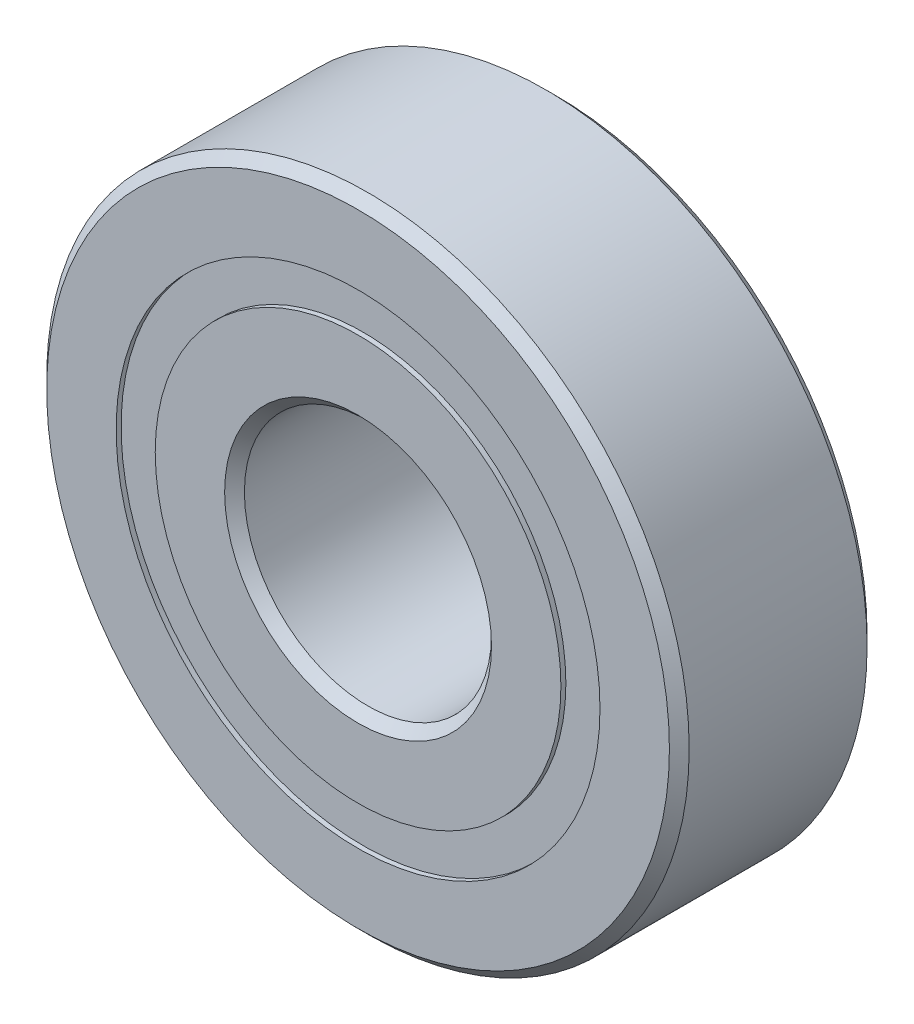
SolidWorks part; units mm, degrees
ref_plane "Front Plane" through (0, 0, 0) normal (0, 0, 1) x (1, 0, 0)
ref_plane "Top Plane" through (0, 0, 0) normal (0, 1, 0) x (1, 0, 0)
ref_plane "Right Plane" through (0, 0, 0) normal (1, 0, 0) x (0, 0, -1)
sketch "Sketch1" plane through (0, 0, 0) normal (1, 0, 0) x (0, 0, -1)
  line L0 (-4, 0) -> (4, 0) construction
  line L1 (0, 13) -> (0, -13) construction
  line L2 (3.6, 13) -> (-3.6, 13)
  line L3 (-3.6, 13) -> (-4, 12.6)
  line L5 (1.7778, 12.6) -> (4, 12.6)
  line L8 (3.6, 13) -> (4, 12.6)
  line L9 (0, 13) -> (0, 9) construction
  line L10 (0, 9) -> (0, 5) construction
  line L11 (-4, 12.6) -> (-1.7778, 12.6)
  line L13 (-1.7778, 9.7912) -> (-1.7778, 12.6)
  line L14 (1.7778, 9.7912) -> (1.7778, 12.6)
  arc A0 (-1.7778, 9.7912) -> (1.7778, 9.7912) centre (0, 9) cw
  point P14 (0, 5)
  dimension "D3" = 3.5556
  dimension "Width" = 8
  dimension "OD" = 26
  dimension "D2" = 0.4
  dimension "Shaft Dia" = 10
revolve "Revolve1" add sketch "Sketch1" angle 360 about L0
sketch "Sketch3" plane through (0, 0, 0) normal (1, 0, 0) x (0, 0, -1)
  line L3 (-4, 5.4) -> (-4, 8.2088)
  line L4 (-3.6, 13) -> (-4, 12.6) construction
  line L5 (-4, 5.4) -> (-3.6, 5)
  line L6 (-3.6, 5) -> (3.6, 5)
  line L7 (3.6, 13) -> (3.6, -13) construction
  line L8 (3.6, 5) -> (4, 5.4)
  line L10 (4, 5.4) -> (4, 8.2088)
  line L12 (0, 0) -> (0, 5) construction
  line L13 (3.6, 13) -> (4, 12.6) construction
  line L16 (-4, 8.2088) -> (-1.7778, 8.2088)
  line L18 (1.7778, 8.2088) -> (4, 8.2088)
  arc A2 (-1.7778, 8.2088) -> (1.7778, 8.2088) centre (0, 9) ccw
  dimension "D1" = 3.2088
revolve "Revolve3" add sketch "Sketch3" angle 360 about L0
sketch "Sketch4" plane through (0, 0, 0) normal (1, 0, 0) x (0, 0, -1)
  line L0 (-1.9459, 9) -> (1.9459, 9)
  arc A2 (-1.9459, 9) -> (1.9459, 9) centre (0, 9) cw
  arc A3 (1.7778, 9.7912) -> (-1.7778, 9.7912) centre (0, 9) ccw construction
revolve "Revolve4" add sketch "Sketch4" angle 360 about L0
ref_axis "Axis1" through (0, 0, -4) along (0, 0, 1)
pattern_circular "CirPattern1" count 12 over 360 about axis through (0, 0, -4) along (0, 0, 1) of bodies 104
sketch "Sketch6" plane through (0, 0, 0) normal (1, 0, 0) x (0, 0, -1)
  line L1 (-3.8, 9.79) -> (-4, 9.79)
  line L2 (-4, 12.6) -> (-4, -12.6) construction
  line L3 (-4, 9.79) -> (-4, 12.6)
  line L4 (3.8, 9.79) -> (4, 9.79)
  line L7 (4, 12.6) -> (4, -12.6) construction
  line L8 (-4, 8.2088) -> (4, 8.2088) construction
  line L9 (4, 9.79) -> (4, 12.6)
  line L12 (-3.6, 13) -> (-4, 12.6) construction
  line L13 (-4, 12.6) -> (4, 12.6)
  line L15 (-3.8, 8.21) -> (-3.8, 9.79)
  line L16 (1.9459, 9.1265) -> (1.9459, 8.21)
  line L17 (-1.9459, 9.1265) -> (-1.9459, 8.21)
  line L18 (3.8, 8.21) -> (3.8, 9.79)
  line L21 (-3.8, 8.21) -> (-1.9459, 8.21)
  line L22 (3.8, 8.21) -> (1.9459, 8.21)
  arc A0 (1.9459, 9.1265) -> (-1.9459, 9.1265) centre (0, 9) ccw
  point P18 (-3.8, 12.8)
  dimension "D1" = 2.81
  dimension "D2" = 1.58
revolve "Revolve5" add sketch "Sketch6" angle 360 about L0
